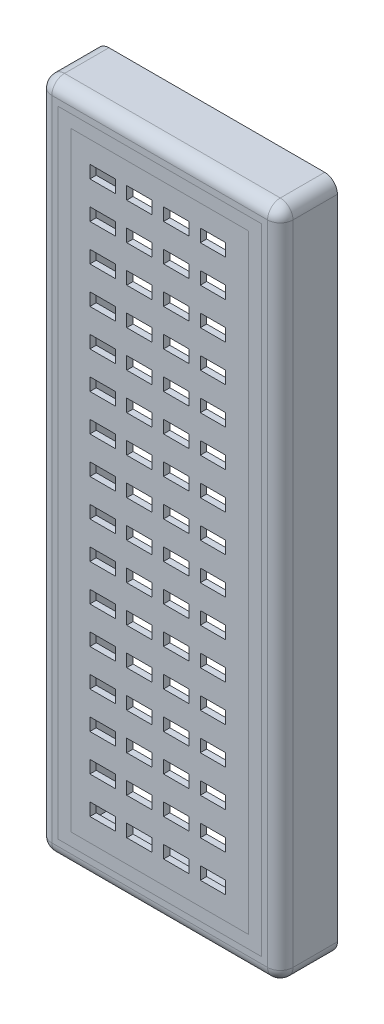
SolidWorks part; units mm, degrees
ref_plane "Front Plane" through (0, 0, 0) normal (0, 0, 1) x (1, 0, 0)
ref_plane "Top Plane" through (0, 0, 0) normal (0, 1, 0) x (1, 0, 0)
ref_plane "Right Plane" through (0, 0, 0) normal (1, 0, 0) x (0, 0, -1)
sketch "Sketch1" plane through (0, 0, 0) normal (0, 0, 1) x (1, 0, 0)
  line L0 (-19.05, 19.05) -> (222.25, 19.05)
  line L1 (0, 0) -> (203.2, 0)
  line L2 (0, 0) -> (0, -635)
  line L3 (0, -635) -> (203.2, -635)
  line L4 (203.2, 0) -> (203.2, -635)
  line L5 (222.25, 19.05) -> (222.25, -654.05)
  line L6 (-19.05, -654.05) -> (222.25, -654.05)
  line L7 (-19.05, 19.05) -> (-19.05, -654.05)
  dimension "D1" = 203.2
  dimension "D2" = 635
  dimension "D3" = 19.05
extrude "Boss-Extrude1" add sketch "Sketch1" along normal blind 50.8
sketch "Sketch2" plane through (0, 0, 50.8) normal (0, 0, 1) x (1, 0, 0)
  line L1 (-19.05, 19.05) -> (222.25, 19.05)
  line L2 (-19.05, 19.05) -> (-19.05, -654.05)
  line L3 (-19.05, -654.05) -> (222.25, -654.05)
  line L4 (222.25, 19.05) -> (222.25, -654.05)
extrude "Boss-Extrude2" add sketch "Sketch2" along normal blind 6.35
sketch "Sketch3" plane through (0, 0, 57.15) normal (0, 0, 1) x (1, 0, 0)
  line L19 (0, -635) -> (203.2, -635) construction
  line L20 (203.2, -635) -> (203.2, 0) construction
  line L21 (0, 0) -> (0, -635) construction
  line L22 (203.2, 0) -> (0, 0) construction
  line L23 (12.7, -622.3) -> (190.5, -622.3)
  line L24 (190.5, -622.3) -> (190.5, -12.7)
  line L25 (12.7, -12.7) -> (12.7, -622.3)
  line L26 (190.5, -12.7) -> (12.7, -12.7)
  line L27 (12.7, -622.3) -> (190.5, -622.3)
  line L28 (190.5, -622.3) -> (190.5, -12.7)
  line L29 (12.7, -12.7) -> (12.7, -622.3)
  line L30 (190.5, -12.7) -> (12.7, -12.7)
  line L31 (0, -635) -> (203.2, -635)
  line L32 (203.2, -635) -> (203.2, 0)
  line L33 (0, 0) -> (0, -635)
  line L34 (203.2, 0) -> (0, 0)
  dimension "D1" = 12.7
split line "Split Line2"
sketch "Sketch5" plane through (0, 0, 57.15) normal (0, 0, 1) x (1, 0, 0)
  line L1 (31.75, -34.29) -> (57.15, -34.29)
  line L2 (31.75, -34.29) -> (31.75, -46.99)
  line L3 (31.75, -46.99) -> (57.15, -46.99)
  line L4 (57.15, -34.29) -> (57.15, -46.99)
  line L5 (12.7, -12.7) -> (190.5, -12.7) construction
  line L6 (44.45, -12.7) -> (44.45, -34.29) construction
  dimension "D1" = 12.7
  dimension "D2" = 12.7
  dimension "D3" = 31.75
  dimension "D4" = 21.59
extrude "Cut-Extrude2" cut sketch "Sketch5" against normal blind 33.02
pattern_linear "LPattern1" count 16 spacing 36.83 along (0, -1, 0) count 4 spacing 36.83 along (1, 0, 0) of "Cut-Extrude2"
fillet "Fillet1" radius 12.7 4 edges at (222.25, -317.5, 57.15) (101.6, -654.05, 57.15) (-19.05, -317.5, 57.15) (101.6, 19.05, 57.15)
fillet "Fillet2" radius 12.7 8 edges at (218.5303, 15.3303, 53.4303) (218.5303, -650.3303, 53.4303) (-15.3303, -650.3303, 53.4303) (-15.3303, 15.3303, 53.4303) (222.25, 19.05, 22.225) (222.25, -654.05, 22.225) (-19.05, -654.05, 22.225) (-19.05, 19.05, 22.225)
